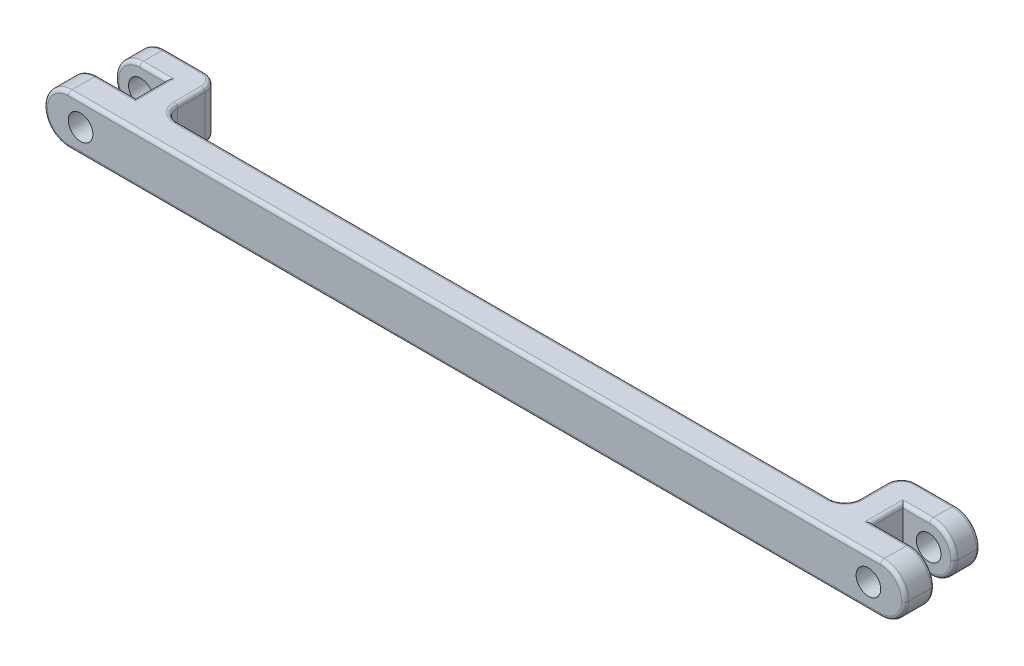
SolidWorks part; units mm, degrees
material "A286 Demir Tabanlı Süperalaşım"
ref_plane "Ön Düzlem" through (0, 0, 0) normal (0, 0, 1) x (1, 0, 0)
ref_plane "Üst Düzlem" through (0, 0, 0) normal (0, 1, 0) x (1, 0, 0)
ref_plane "Sağ Düzlem" through (0, 0, 0) normal (1, 0, 0) x (0, 0, -1)
sketch "Çizim2" plane through (0, 0, 0) normal (0, 1, 0) x (1, 0, 0)
  line L0 (-585.82, 0) -> (585.82, 0)
  line L1 (585.82, 0) -> (585.82, 40)
  line L2 (585.82, 40) -> (500.82, 40)
  line L3 (500.82, 40) -> (500.82, 82)
  line L4 (500.82, 82) -> (570.82, 82)
  line L5 (570.82, 82) -> (570.82, 117)
  line L6 (570.82, 117) -> (463.82, 117)
  line L7 (463.82, 117) -> (463.82, 40)
  line L8 (463.82, 40) -> (-463.82, 40)
  line L9 (535.82, 117) -> (535.82, 0) construction
  line L10 (463.82, 40) -> (463.1576, 40.4117)
  line L11 (0, 0) -> (0, 256.4103) construction
  line L13 (-463.82, 40) -> (-463.1576, 40.4117)
  line L14 (-463.82, 117) -> (-463.82, 40)
  line L15 (-570.82, 117) -> (-463.82, 117)
  line L16 (-570.82, 82) -> (-570.82, 117)
  line L17 (-500.82, 82) -> (-570.82, 82)
  line L18 (-500.82, 40) -> (-500.82, 82)
  line L19 (-585.82, 40) -> (-500.82, 40)
  line L20 (-585.82, 0) -> (-585.82, 40)
  point P19 (0, 40)
  dimension "D1" = 585.82
  dimension "D2" = 40
  dimension "D3" = 35
  dimension "D4" = 42
  dimension "D5" = 90
  dimension "D6" = 35
  dimension "D7" = 85
  dimension "D8" = 70
  dimension "D9" = 107
  dimension "D10" = 40
extrude "Yükseklik-Ekstrüzyon1" add sketch "Çizim2" along normal blind 67 contours L0 L11 L8 L14 L15 L16 L17 L18 L19 L20 | L11 L0 L1 L2 L3 L4 L5 L6 L7 L8 region at (0, 0, -32.5798)
sketch "Çizim3" plane through (0, 0, -117) normal (0, 0, -1) x (-1, 0, 0)
  line L0 (-570.82, 67) -> (-570.82, 0) construction
  line L1 (-570.82, 67) -> (-463.82, 67) construction
  line L2 (0, 0) -> (0, 101.5751) construction
  circle A0 centre (-535.82, 33.5) radius 16.75
  circle A1 centre (535.82, 33.5) radius 16.75
  point P2 (-570.82, 33.5)
  dimension "D1" = 35
  dimension "D3" = 33.5
  dimension "D2" = 33.5
extrude "Kes-Ekstrüzyon1" cut sketch "Çizim3" against normal up to surface (117 mm away) up to face at (0, 33.5, 0)
fillet "Radyus1" radius 20 4 edges at (463.82, 33.5, -117) (463.82, 33.5, -40) (-463.82, 33.5, -117) (-463.82, 33.5, -40)
fillet "Radyus2" radius 33.5 8 edges at (-585.82, 0, -20) (-585.82, 67, -20) (585.82, 0, -20) (585.82, 67, -20) (570.82, 67, -99.5) (570.82, 0, -99.5) (-570.82, 0, -99.5) (-570.82, 67, -99.5)
fillet "Radyus4" radius 5 46 edges at (561.0081, 57.1881, -117) (561.0081, 9.8119, -117) (510.57, 0, -117) (469.6779, 0, -111.1421) (463.82, 0, -78.5) (457.9621, 0, -45.8579) (0, 0, -40) (-457.9621, 0, -45.8579) (-463.82, 0, -78.5) (-469.6779, 0, -111.1421) (-510.57, 0, -117) (-561.0081, 9.8119, -117) (-561.0081, 57.1881, -117) (576.0081, 57.1881, -40) (576.0081, 9.8119, -40) (526.57, 0, -40) (519.07, 0, -82) (561.0081, 9.8119, -82) (561.0081, 57.1881, -82) (-576.0081, 57.1881, 0) (-576.0081, 9.8119, 0) (0, 0, 0) (576.0081, 9.8119, 0) (576.0081, 57.1881, 0) (-576.0081, 57.1881, -40) (-576.0081, 9.8119, -40) (-526.57, 0, -40) (-519.07, 0, -82) (-561.0081, 9.8119, -82) (-561.0081, 57.1881, -82) (-500.82, 67, -61) (-519.07, 67, -82) (-510.57, 67, -117) (-469.6779, 67, -111.1421) (-463.82, 67, -78.5) (-457.9621, 67, -45.8579) (0, 67, -40) (457.9621, 67, -45.8579) (463.82, 67, -78.5) (469.6779, 67, -111.1421) (510.57, 67, -117) (519.07, 67, -82) (500.82, 67, -61) (526.57, 67, -40) (0, 67, 0) (-526.57, 67, -40)
